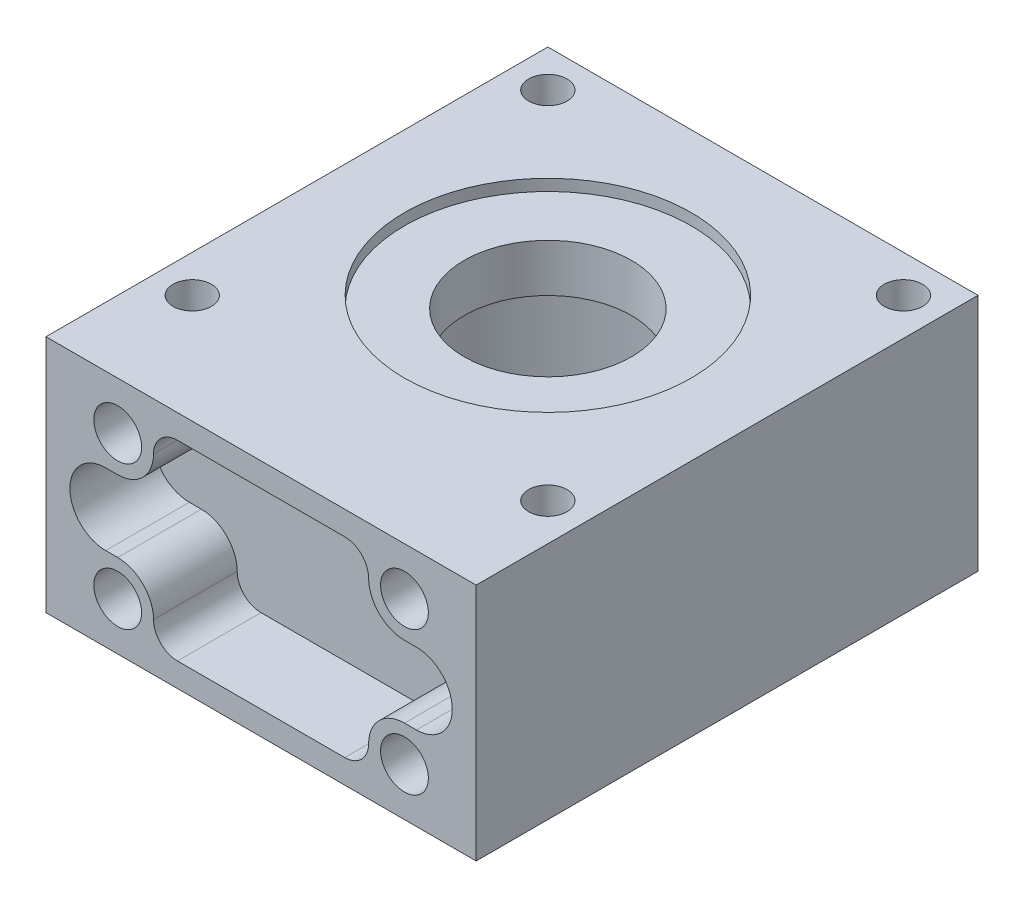
SolidWorks part; units mm, degrees
material "6061 Alloy"
ref_plane "Front" through (0, 0, 0) normal (0, 0, 1) x (1, 0, 0)
ref_plane "Top" through (0, 0, 0) normal (0, 1, 0) x (1, 0, 0)
ref_plane "Right" through (0, 0, 0) normal (1, 0, 0) x (0, 0, -1)
sketch "Sketch1" plane through (0, 0, 0) normal (0, 1, 0) x (1, 0, 0)
  line L0 (28.575, 28.575) -> (-28.575, 28.575)
  line L1 (-28.575, 28.575) -> (28.575, 28.575) construction
  line L2 (-28.575, 28.575) -> (-28.575, -28.575)
  line L3 (-28.575, -28.575) -> (28.575, -28.575) construction
  line L4 (28.575, 28.575) -> (28.575, -28.575)
  line L5 (-28.575, 28.575) -> (28.575, -28.575) construction
  line L6 (-28.575, -28.575) -> (28.575, 28.575) construction
  line L7 (-23.622, 23.622) -> (23.622, 23.622) construction
  line L8 (-23.622, 23.622) -> (-23.622, -23.622) construction
  line L9 (-23.622, -23.622) -> (23.622, -23.622) construction
  line L10 (23.622, 23.622) -> (23.622, -23.622) construction
  line L11 (-23.622, 23.622) -> (23.622, -23.622) construction
  line L12 (-23.622, -23.622) -> (23.622, 23.622) construction
  line L15 (-28.575, -28.575) -> (-28.575, -38.1)
  line L16 (-28.575, -38.1) -> (28.575, -38.1)
  line L17 (28.575, -38.1) -> (28.575, -28.575)
  circle A0 centre (23.622, -23.622) radius 2.5527
  circle A1 centre (23.622, 23.622) radius 2.5527
  circle A2 centre (-23.622, 23.622) radius 2.5527
  circle A3 centre (-23.622, -23.622) radius 2.5527
  point P0 (0, 0)
  point P6 (0, 0)
  dimension "D3" = 5.1054
  dimension "D1" = 57.15
  dimension "D2" = 47.244
  dimension "D4" = 9.525
extrude "Boss-Extrude1" add sketch "Sketch1" along normal blind 31.75
sketch "Sketch2" plane through (0, 31.75, 0) normal (0, 1, 0) x (1, 0, 0)
  circle A0 centre (0, 0) radius 19.05
  dimension "D1" = 38.1
extrude "Cut-Extrude1" cut sketch "Sketch2" against normal blind 1.524
sketch "Sketch3" plane through (0, 30.226, 0) normal (0, 1, 0) x (1, 0, 0)
  circle A0 centre (0, 0) radius 11.1125
  dimension "D1" = 22.225
extrude "Cut-Extrude2" cut sketch "Sketch3" against normal through all
sketch "Sketch4" plane through (0, 0, 0) normal (0, -1, 0) x (1, 0, 0)
  line L0 (0, 0) -> (0, 28.575) construction
  line L2 (0, 0) -> (13.0457, 20.2994) construction
  line L5 (-28.575, 28.575) -> (28.575, 28.575) construction
  circle A0 centre (0, 0) radius 21.844 construction
  circle A1 centre (0, 0) radius 24.13 construction
  arc A2 (0, 20.955) -> (2.8224, 22.6758) centre (0, 24.13) ccw
  arc A3 (11.3291, 17.6285) -> (9.8851, 20.602) centre (13.0457, 20.2994) cw
  arc A4 (2.8224, 22.6758) -> (9.8851, 20.602) centre (6.1542, 20.9592) cw
  arc A5 (11.3291, 17.6285) -> (14.6338, 17.5502) centre (13.0457, 20.2994) ccw
  arc A6 (14.6338, 17.5502) -> (19.4542, 11.9872) centre (16.5086, 14.3048) cw
  arc A7 (19.0613, 8.705) -> (19.4542, 11.9872) centre (21.9494, 10.024) cw
  arc A8 (19.0613, 8.705) -> (21.7991, 6.8525) centre (21.9494, 10.024) ccw
  arc A9 (21.7991, 6.8525) -> (22.8467, -0.4334) centre (21.6217, 3.1087) cw
  arc A10 (20.7417, -2.9822) -> (22.8467, -0.4334) centre (23.8844, -3.4341) cw
  arc A11 (20.7417, -2.9822) -> (22.0433, -6.0208) centre (23.8844, -3.4341) ccw
  arc A12 (22.0433, -6.0208) -> (18.9855, -12.7165) centre (19.87, -9.0743) cw
  arc A13 (15.8367, -13.7226) -> (18.9855, -12.7165) centre (18.2362, -15.8018) cw
  arc A14 (15.8367, -13.7226) -> (15.289, -16.9825) centre (18.2362, -15.8018) ccw
  arc A15 (15.289, -16.9825) -> (9.0966, -20.9621) centre (11.8098, -18.3763) cw
  arc A16 (5.9037, -20.1062) -> (9.0966, -20.9621) centre (6.7982, -23.1526) cw
  arc A17 (5.9037, -20.1062) -> (3.6804, -22.5524) centre (6.7982, -23.1526) ccw
  arc A18 (3.6804, -22.5524) -> (-3.6804, -22.5524) centre (0, -21.844) cw
  arc A19 (-5.9037, -20.1062) -> (-3.6804, -22.5524) centre (-6.7982, -23.1526) cw
  arc A20 (-5.9037, -20.1062) -> (-9.0966, -20.9621) centre (-6.7982, -23.1526) ccw
  arc A21 (-9.0966, -20.9621) -> (-15.289, -16.9825) centre (-11.8098, -18.3763) cw
  arc A22 (-15.8367, -13.7226) -> (-15.289, -16.9825) centre (-18.2362, -15.8018) cw
  arc A23 (-15.8367, -13.7226) -> (-18.9855, -12.7165) centre (-18.2362, -15.8018) ccw
  arc A24 (-18.9855, -12.7165) -> (-22.0433, -6.0208) centre (-19.87, -9.0743) cw
  arc A25 (-20.7417, -2.9822) -> (-22.0433, -6.0208) centre (-23.8844, -3.4341) cw
  arc A26 (-20.7417, -2.9822) -> (-22.8467, -0.4334) centre (-23.8844, -3.4341) ccw
  arc A27 (-22.8467, -0.4334) -> (-21.7991, 6.8525) centre (-21.6217, 3.1087) cw
  arc A28 (-19.0613, 8.705) -> (-21.7991, 6.8525) centre (-21.9494, 10.024) cw
  arc A29 (-19.0613, 8.705) -> (-19.4542, 11.9872) centre (-21.9494, 10.024) ccw
  arc A30 (-19.4542, 11.9872) -> (-14.6338, 17.5502) centre (-16.5086, 14.3048) cw
  arc A31 (-11.3291, 17.6285) -> (-14.6338, 17.5502) centre (-13.0457, 20.2994) cw
  arc A32 (-11.3291, 17.6285) -> (-9.8851, 20.602) centre (-13.0457, 20.2994) ccw
  arc A33 (-9.8851, 20.602) -> (-2.8224, 22.6758) centre (-6.1542, 20.9592) cw
  arc A34 (0, 20.955) -> (-2.8224, 22.6758) centre (0, 24.13) cw
  point P14 (0, 28.575)
  point P87 (0, 0)
  dimension "D1" = 48.26
  dimension "D2" = 43.688
  dimension "D4" = 3.175
  dimension "D5" = 3.175
  dimension "D3" = 32.727
  dimension "D6" = 11
extrude "Cut-Extrude3" cut sketch "Sketch4" against normal blind 23.876
sketch "Sketch5" plane through (0, 0, 0) normal (0, -1, 0) x (1, 0, 0)
  circle A0 centre (0, 0) radius 26.1937
  dimension "D1" = 52.3875
extrude "Cut-Extrude4" cut sketch "Sketch5" against normal blind 17.526
sketch "Sketch7" plane through (0, 0, 0) normal (0, -1, 0) x (1, 0, 0)
  line L0 (-28.575, -28.575) -> (28.575, -28.575) construction
  line L4 (-28.575, -28.575) -> (-28.575, 38.1) construction
  line L5 (-23.8125, 26.9875) -> (23.8125, 26.9875)
  line L6 (-26.9875, 23.8125) -> (-26.9875, -23.8125)
  line L7 (-23.8125, -26.9875) -> (23.8125, -26.9875)
  line L8 (26.9875, 23.8125) -> (26.9875, -23.8125)
  line L9 (-26.9875, 26.9875) -> (26.9875, -26.9875) construction
  line L10 (-26.9875, -26.9875) -> (26.9875, 26.9875) construction
  arc A0 (-26.9875, -23.8125) -> (-23.8125, -26.9875) centre (-23.8125, -23.8125) ccw
  arc A2 (23.8125, -26.9875) -> (26.9875, -23.8125) centre (23.8125, -23.8125) ccw
  arc A3 (23.8125, 26.9875) -> (26.9875, 23.8125) centre (23.8125, 23.8125) cw
  arc A4 (-23.8125, 26.9875) -> (-26.9875, 23.8125) centre (-23.8125, 23.8125) ccw
  point P0 (0, 0)
  dimension "D1" = 1.5875
  dimension "D3" = 3.175
  dimension "D2" = 1.5875
extrude "Cut-Extrude5" cut sketch "Sketch7" against normal blind 1.5875
ref_plane "Plane1" through (0, 0, 28.575) normal (0, 0, 1) x (1, 0, 0)
sketch "Sketch10" plane through (0, 0, 38.1) normal (0, 0, 1) x (1, 0, 0)
  line L0 (28.575, 31.75) -> (28.575, 0) construction
  line L1 (19.05, 25.4) -> (-19.05, 25.4)
  line L2 (19.05, 25.4) -> (19.05, 6.35)
  line L3 (19.05, 6.35) -> (-19.05, 6.35)
  line L4 (-19.05, 25.4) -> (-19.05, 6.35)
  line L5 (19.05, 25.4) -> (-19.05, 6.35) construction
  line L6 (19.05, 6.35) -> (-19.05, 25.4) construction
  line L7 (-28.575, 0) -> (28.575, 0) construction
  point P0 (0, 15.875)
  point P7 (28.575, 15.875)
  point P10 (0, 0)
  dimension "D1" = 38.1
  dimension "D2" = 19.05
hole_wizard "1/4-20 Tapped Hole1" positions "Sketch12" profile "Sketch11" tap size "1/4-20" standard "ANSI Inch"
sketch "Sketch12" plane through (0, 0, 38.1) normal (0, 0, 1) x (1, 0, 0)
  point P0 (-19.05, 25.4)
  point P3 (19.05, 25.4)
  point P6 (19.05, 6.35)
  point P9 (-19.05, 6.35)
sketch "Sketch11" plane through (-19.05, 25.4, 38.1) normal (1, 0, 0) x (0, -1, 0)
  line L0 (0, 0) -> (0, 11.1858)
  line L1 (0, 11.1858) -> (2.5527, 9.652)
  line L2 (2.5527, 9.652) -> (2.5527, 9.525)
  line L3 (2.5527, 9.525) -> (3.175, 9.525)
  line L4 (3.175, 9.525) -> (3.175, 0)
  line L5 (3.175, 0) -> (0, 0)
  line L10 (0, 11.1858) -> (-2.5527, 9.652) construction
  line L11 (0, -6.35) -> (0, 107.95) construction
  dimension "Tap Drill Dia." = 5.1054
  dimension "Tap Drill Depth" = 9.652
  dimension "Thread Major Dia." = 6.35
  dimension "Thread Depth" = 9.525
  dimension "Drill Angle" = 118
sketch "Sketch13" plane through (0, 0, 38.1) normal (0, 0, 1) x (1, 0, 0)
  line L0 (-28.575, 15.875) -> (0, 15.875) construction
  line L1 (-28.575, 31.75) -> (-28.575, 0) construction
  line L2 (0, 15.875) -> (0, 0) construction
  line L3 (-20.6375, 11.1125) -> (-19.05, 11.1125)
  line L4 (-11.1125, 28.575) -> (11.1125, 28.575)
  line L5 (-11.1125, 3.175) -> (11.1125, 3.175)
  line L6 (-28.575, 0) -> (28.575, 0) construction
  line L7 (-20.6375, 20.6375) -> (-19.05, 20.6375)
  line L8 (20.6375, 11.1125) -> (19.05, 11.1125)
  line L9 (20.6375, 20.6375) -> (19.05, 20.6375)
  arc A0 (-20.6375, 20.6375) -> (-20.6375, 11.1125) centre (-20.6375, 15.875) ccw
  arc A1 (-19.05, 11.1125) -> (-14.2875, 6.35) centre (-19.05, 6.35) cw
  arc A2 (-14.2875, 6.35) -> (-11.1125, 3.175) centre (-11.1125, 6.35) ccw
  arc A3 (-14.2875, 25.4) -> (-11.1125, 28.575) centre (-11.1125, 25.4) cw
  arc A4 (-19.05, 20.6375) -> (-14.2875, 25.4) centre (-19.05, 25.4) ccw
  arc A5 (14.2875, 6.35) -> (11.1125, 3.175) centre (11.1125, 6.35) cw
  arc A6 (19.05, 11.1125) -> (14.2875, 6.35) centre (19.05, 6.35) ccw
  arc A7 (20.6375, 20.6375) -> (20.6375, 11.1125) centre (20.6375, 15.875) cw
  arc A8 (19.05, 20.6375) -> (14.2875, 25.4) centre (19.05, 25.4) cw
  arc A9 (14.2875, 25.4) -> (11.1125, 28.575) centre (11.1125, 25.4) ccw
  point P14 (-25.4, 15.875)
  point P23 (0, 3.175)
  point P35 (0, 28.575)
  dimension "D1" = 3.175
  dimension "D2" = 3.175
  dimension "D3" = 4.7625
  dimension "D4" = 3.175
extrude "Cut-Extrude6" cut sketch "Sketch13" against normal blind 11.1125
